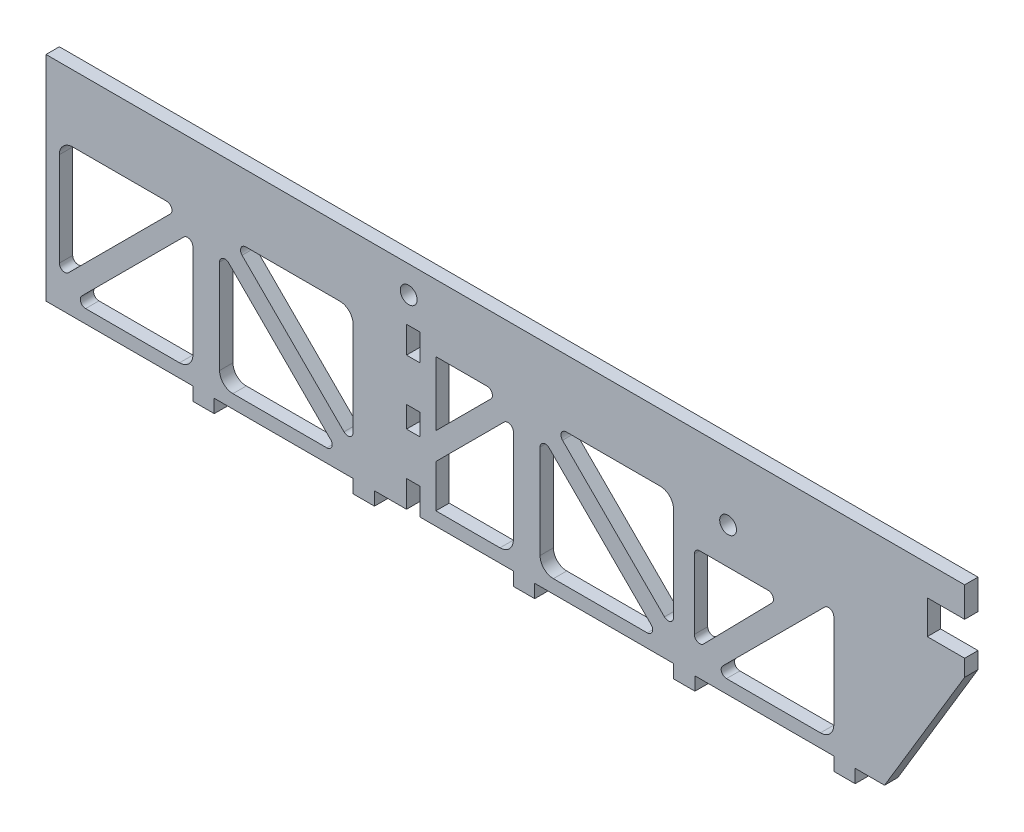
SolidWorks part; units mm, degrees
material "Pine"
ref_plane "Front Plane" through (0, 0, 0) normal (0, 0, 1) x (1, 0, 0)
ref_plane "Top Plane" through (0, 0, 0) normal (0, 1, 0) x (1, 0, 0)
ref_plane "Right Plane" through (0, 0, 0) normal (1, 0, 0) x (0, 0, -1)
sketch "Model" plane through (0, 0, 0) normal (0, 0, 1) x (1, 0, 0)
  line L0 (312.6855, 15.1239) -> (345.2281, 48.2988)
  line L1 (343.4149, 52.6175) -> (310.8722, 52.6175)
  line L2 (308.3322, 50.0775) -> (308.3322, 16.9026)
  line L8 (171.2321, 6.35) -> (215.9, 6.35)
  line L9 (217.9139, 59.1639) -> (169.4361, 10.6861)
  line L10 (222.25, 57.3679) -> (222.25, 12.7)
  line L11 (234.95, 57.3679) -> (234.95, 12.7)
  line L12 (239.2861, 59.1639) -> (287.7639, 10.6861)
  line L13 (241.3, 6.35) -> (285.9679, 6.35)
  line L14 (294.1139, 17.0361) -> (245.6361, 65.5139)
  line L15 (247.4321, 69.85) -> (292.1, 69.85)
  line L16 (298.45, 63.5) -> (298.45, 18.8321)
  line L17 (323.6321, 6.35) -> (368.3, 6.35)
  line L18 (370.3139, 59.1639) -> (321.8361, 10.6861)
  line L19 (374.65, 57.3679) -> (374.65, 12.7)
  line L20 (18.8321, 6.35) -> (63.5, 6.35)
  line L21 (17.0361, 10.6861) -> (65.5139, 59.1639)
  line L22 (69.85, 57.3679) -> (69.85, 12.7)
  line L23 (82.55, 57.3679) -> (82.55, 12.7)
  line L24 (86.8861, 59.1639) -> (135.3639, 10.6861)
  line L25 (88.9, 6.35) -> (133.5679, 6.35)
  line L26 (93.2361, 65.5139) -> (141.7139, 17.0361)
  line L27 (95.0321, 69.85) -> (139.7, 69.85)
  line L28 (146.05, 63.5) -> (146.05, 18.8321)
  line L29 (163.0861, 17.0361) -> (211.5639, 65.5139)
  line L30 (158.75, 63.5) -> (158.75, 18.8321)
  line L31 (165.1, 69.85) -> (209.7679, 69.85)
  line L35 (419.1, 87.376) -> (419.1, 71.374)
  line L36 (436.88, 87.376) -> (419.1, 87.376)
  line L37 (436.88, 87.376) -> (436.88, 95.25)
  line L38 (0, 95.25) -> (436.88, 95.25)
  line L39 (0, 0) -> (0, 95.25)
  line L40 (0, 0) -> (398.78, 0)
  line L41 (436.88, 63.5) -> (398.78, 0)
  line L42 (436.88, 63.5) -> (436.88, 71.374)
  line L43 (419.1, 71.374) -> (436.88, 71.374)
  line L44 (6.35, 63.5) -> (6.35, 18.8321)
  line L45 (12.7, 69.85) -> (57.3679, 69.85)
  line L46 (59.1639, 65.5139) -> (10.6861, 17.0361)
  arc A0 (215.9, 6.35) -> (222.25, 12.7) centre (215.9, 12.7) ccw
  arc A1 (169.4361, 10.6861) -> (171.2321, 6.35) centre (171.2321, 8.89) ccw
  arc A2 (222.25, 57.3679) -> (217.9139, 59.1639) centre (219.71, 57.3679) ccw
  arc A3 (239.2861, 59.1639) -> (234.95, 57.3679) centre (237.49, 57.3679) ccw
  arc A4 (285.9679, 6.35) -> (287.7639, 10.6861) centre (285.9679, 8.89) ccw
  arc A5 (234.95, 12.7) -> (241.3, 6.35) centre (241.3, 12.7) ccw
  arc A6 (247.4321, 69.85) -> (245.6361, 65.5139) centre (247.4321, 67.31) ccw
  arc A7 (298.45, 63.5) -> (292.1, 69.85) centre (292.1, 63.5) ccw
  arc A8 (294.1139, 17.0361) -> (298.45, 18.8321) centre (295.91, 18.8321) ccw
  arc A9 (321.8361, 10.6861) -> (323.6321, 6.35) centre (323.6321, 8.89) ccw
  arc A10 (374.65, 57.3679) -> (370.3139, 59.1639) centre (372.11, 57.3679) ccw
  arc A11 (368.3, 6.35) -> (374.65, 12.7) centre (368.3, 12.7) ccw
  arc A12 (63.5, 6.35) -> (69.85, 12.7) centre (63.5, 12.7) ccw
  arc A13 (17.0361, 10.6861) -> (18.8321, 6.35) centre (18.8321, 8.89) ccw
  arc A14 (69.85, 57.3679) -> (65.5139, 59.1639) centre (67.31, 57.3679) ccw
  arc A15 (86.8861, 59.1639) -> (82.55, 57.3679) centre (85.09, 57.3679) ccw
  arc A16 (133.5679, 6.35) -> (135.3639, 10.6861) centre (133.5679, 8.89) ccw
  arc A17 (82.55, 12.7) -> (88.9, 6.35) centre (88.9, 12.7) ccw
  arc A18 (95.0321, 69.85) -> (93.2361, 65.5139) centre (95.0321, 67.31) ccw
  arc A19 (146.05, 63.5) -> (139.7, 69.85) centre (139.7, 63.5) ccw
  arc A20 (141.7139, 17.0361) -> (146.05, 18.8321) centre (143.51, 18.8321) ccw
  arc A21 (158.75, 18.8321) -> (163.0861, 17.0361) centre (161.29, 18.8321) ccw
  arc A22 (165.1, 69.85) -> (158.75, 63.5) centre (165.1, 63.5) ccw
  arc A23 (211.5639, 65.5139) -> (209.7679, 69.85) centre (209.7679, 67.31) ccw
  arc A24 (345.2281, 48.2988) -> (343.4149, 52.6175) centre (343.4149, 50.0775) ccw
  arc A25 (310.8722, 52.6175) -> (308.3322, 50.0775) centre (310.8722, 50.0775) ccw
  arc A26 (312.6855, 15.1239) -> (308.3322, 16.9026) centre (310.8722, 16.9026) cw
  arc A27 (6.35, 18.8321) -> (10.6861, 17.0361) centre (8.89, 18.8321) ccw
  arc A28 (12.7, 69.85) -> (6.35, 63.5) centre (12.7, 63.5) ccw
  arc A29 (59.1639, 65.5139) -> (57.3679, 69.85) centre (57.3679, 67.31) ccw
  circle A30 centre (172.4917, 88.8013) radius 4
  circle A31 centre (324.3837, 70.0053) radius 4
  dimension "D2" = 6.4487
  dimension "D3" = 172.4917
  dimension "D4" = 8
  dimension "D5" = 18.796
  dimension "D6" = 8
  dimension "D8" = 2.54
  dimension "D1" = 95.25
  dimension "D7" = 151.892
extrude "Boss-Extrude2" add sketch "Model" along normal blind 6.35
sketch "Sketch1" plane through (0, 0, 6.35) normal (0, 0, 1) x (1, 0, 0)
  line L0 (69.85, 12.7) -> (69.85, 0) construction
  line L1 (146.05, 95.25) -> (146.05, 0) construction
  line L2 (146.05, 18.8321) -> (146.05, 63.5) construction
  line L3 (0, 0) -> (398.78, 0) construction
  line L4 (222.25, 95.25) -> (222.25, 0) construction
  line L5 (222.25, 12.7) -> (222.25, 57.3679) construction
  line L6 (298.45, 18.8321) -> (298.45, 0) construction
  line L7 (146.05, 0) -> (156.21, 0)
  line L8 (69.85, 0) -> (80.01, 0)
  line L9 (69.85, 0) -> (69.85, -6.35)
  line L10 (69.85, -6.35) -> (80.01, -6.35)
  line L11 (80.01, 0) -> (80.01, -6.35)
  line L16 (222.25, 0) -> (232.41, 0)
  line L17 (222.25, 0) -> (222.25, -6.35)
  line L18 (222.25, -6.35) -> (232.41, -6.35)
  line L19 (232.41, 0) -> (232.41, -6.35)
  line L20 (146.05, 0) -> (146.05, -6.35)
  line L21 (146.05, -6.35) -> (156.21, -6.35)
  line L22 (156.21, 0) -> (156.21, -6.35)
  line L24 (374.65, 12.7) -> (374.65, 0) construction
  line L25 (374.65, 12.7) -> (374.65, 57.3679) construction
  line L27 (298.45, 0) -> (308.61, 0)
  line L28 (298.45, 0) -> (298.45, -6.35)
  line L29 (298.45, -6.35) -> (308.61, -6.35)
  line L30 (308.61, 0) -> (308.61, -6.35)
  line L31 (374.65, 0) -> (384.81, 0)
  line L32 (374.65, 0) -> (374.65, -6.35)
  line L33 (374.65, -6.35) -> (384.81, -6.35)
  line L34 (384.81, 0) -> (384.81, -6.35)
  line L39 (0, 101.6) -> (436.88, 101.6)
  line L53 (0, 95.25) -> (0, 101.6)
  line L55 (436.88, 95.25) -> (436.88, 101.6)
  line L56 (436.88, 95.25) -> (0, 95.25) construction
  line L57 (0, 95.25) -> (436.88, 95.25)
  arc A0 (368.3, 6.35) -> (374.65, 12.7) centre (368.3, 12.7) ccw construction
  dimension "D1" = 10.16
  dimension "D2" = 6.35
  dimension "D3" = 10.16
  dimension "D4" = 6.35
  dimension "D5" = 10.16
  dimension "D6" = 10.16
  dimension "D7" = 10.16
  dimension "D13" = 6.35
extrude "Boss-Extrude3" add sketch "Sketch1" against normal up to surface (6.35 mm away) up to face at (321.5295, 39.2174, 0)
sketch "Sketch2" plane through (0, 0, 6.35) normal (0, 0, 1) x (1, 0, 0)
  line L0 (156.21, 0) -> (222.25, 0) construction
  line L1 (165.1, 79.7539) -> (185.42, 79.7539)
  line L2 (165.1, 79.7539) -> (165.1, 0)
  line L3 (165.1, 0) -> (185.42, 0)
  line L4 (185.42, 79.7539) -> (185.42, 0)
  line L5 (158.75, 63.5) -> (158.75, 18.8321) construction
  line L7 (171.45, 0) -> (177.8, 0)
  line L8 (171.45, 0) -> (171.45, 12.7)
  line L9 (171.45, 12.7) -> (177.8, 12.7)
  line L10 (177.8, 0) -> (177.8, 12.7)
  line L11 (171.45, 33.02) -> (177.8, 33.02)
  line L12 (171.45, 33.02) -> (171.45, 43.18)
  line L13 (171.45, 43.18) -> (177.8, 43.18)
  line L14 (177.8, 33.02) -> (177.8, 43.18)
  line L15 (171.45, 63.5) -> (177.8, 63.5)
  line L16 (171.45, 63.5) -> (171.45, 76.2)
  line L17 (171.45, 76.2) -> (177.8, 76.2)
  line L18 (177.8, 63.5) -> (177.8, 76.2)
  line L19 (146.05, -6.35) -> (156.21, -6.35) construction
  dimension "D1" = 6.35
  dimension "D2" = 20.32
  dimension "D3" = 6.35
  dimension "D4" = 6.35
  dimension "D5" = 6.35
  dimension "D6" = 12.7
  dimension "D7" = 20.32
  dimension "D8" = 20.32
  dimension "D9" = 10.16
  dimension "D10" = 12.7
extrude "Boss-Extrude4" add sketch "Sketch2" against normal up to surface (6.35 mm away) contours L10 L3 L4 L1 L2 L8 L9 L18 L15 L16 L17 L14 L11 L12 L13 region at (175.26, 78.9309, 6.35) up to face at (321.5295, 39.2174, 0)
extrude "Cut-Extrude1" cut sketch "Sketch2<3>" along direction (0, 0, 1) on the side against the normal up to surface (6.35 mm away) from surface contours L3 L10 L9 L8 | L15 L18 L17 L16 region at (174.625, 6.35, 6.35) region at (174.625, 69.85, 6.35) up to face at (174.625, 9.525, 0) starting at face at (174.625, 9.525, 6.35)
sketch "Sketch2<3>" plane through (0, 0, 6.35) normal (0, 0, 1) x (1, 0, 0) same geometry as "Sketch2"
sketch "Sketch3" plane through (0, 0, 6.35) normal (0, 0, 1) x (1, 0, 0)
  line L1 (154.8502, 72.8404) -> (168.7325, 72.8404)
  line L2 (154.8502, 72.8404) -> (154.8502, 13.7288)
  line L3 (154.8502, 13.7288) -> (168.7325, 13.7288)
  line L4 (168.7325, 72.8404) -> (168.7325, 13.7288)
extrude "Boss-Extrude5" add sketch "Sketch3" against normal up to surface (6.35 mm away) up to face at (174.625, 69.85, 0)
